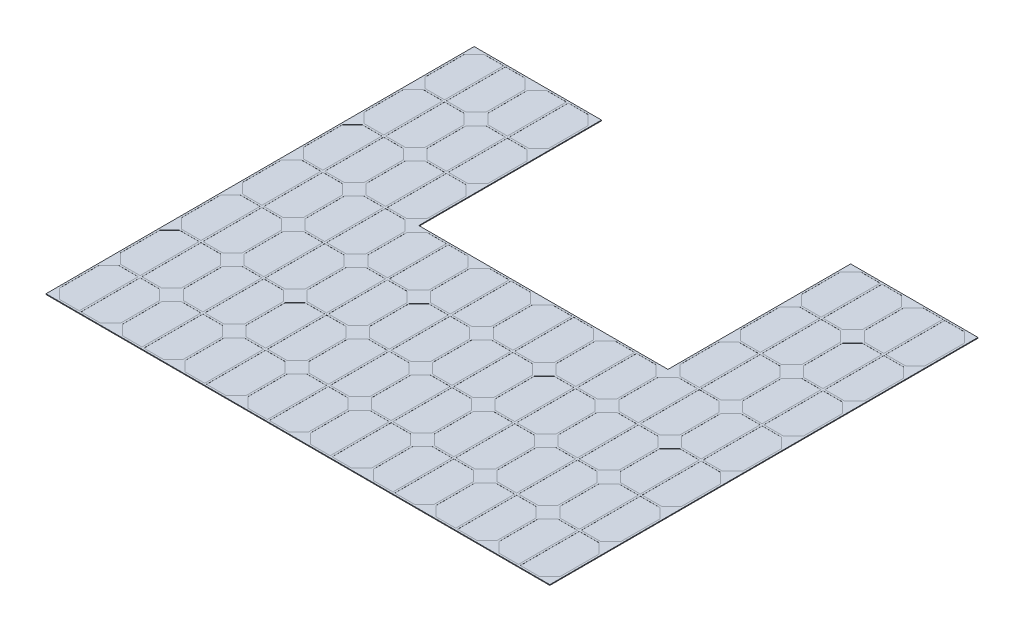
SolidWorks part; units mm, degrees
ref_plane "Front Plane" through (0, 0, 0) normal (0, 0, 1) x (1, 0, 0)
ref_plane "Top Plane" through (0, 0, 0) normal (0, 1, 0) x (1, 0, 0)
ref_plane "Right Plane" through (0, 0, 0) normal (1, 0, 0) x (0, 0, -1)
sketch "Sketch1" plane through (0, 0, 0) normal (0, 1, 0) x (1, 0, 0)
  line L0 (-102.0578, 273.2823) -> (-102.0578, 25.7823)
  line L1 (-274.5578, 273.2823) -> (-102.0578, 273.2823)
  line L2 (-274.5578, 273.2823) -> (-274.5578, -306.7177)
  line L3 (-274.5578, -306.7177) -> (407.9422, -306.7177)
  line L4 (407.9422, 273.2823) -> (407.9422, -306.7177)
  line L5 (-102.0578, 25.7823) -> (235.4422, 25.7823)
  line L6 (235.4422, 25.7823) -> (235.4422, 273.2823)
  line L7 (235.4422, 273.2823) -> (407.9422, 273.2823)
  dimension "D1" = 580
  dimension "D2" = 682.5
  dimension "D3" = 172.5
  dimension "D4" = 172.5
  dimension "D5" = 247.5
extrude "Boss-Extrude1" add sketch "Sketch1" along normal blind 1 contours L2 L3 L4 L7 L6 L5 L0 L1
sketch "Sketch2" plane through (0, 1, 0) normal (0, 1, 0) x (1, 0, 0)
  line L0 (-272.0578, -237.7177) -> (-272.0578, -290.7177)
  line L1 (-272.0578, -290.7177) -> (-258.5578, -304.2177)
  line L2 (-258.5578, -304.2177) -> (-232.0578, -304.2177)
  line L3 (-232.0578, -304.2177) -> (-232.0578, -224.2177)
  line L4 (-232.0578, -224.2177) -> (-258.5578, -224.2177)
  line L5 (-258.5578, -224.2177) -> (-272.0578, -237.7177)
  line L6 (-274.5578, 273.2823) -> (-274.5578, -306.7177) construction
  line L7 (-274.5578, -306.7177) -> (407.9422, -306.7177) construction
  line L8 (-230.8078, -139.2177) -> (-230.8078, -217.2899) construction
  line L9 (-203.0578, -224.2177) -> (-189.5578, -237.7177)
  line L10 (-229.5578, -224.2177) -> (-203.0578, -224.2177)
  line L11 (-229.5578, -304.2177) -> (-229.5578, -224.2177)
  line L12 (-203.0578, -304.2177) -> (-229.5578, -304.2177)
  line L13 (-189.5578, -290.7177) -> (-203.0578, -304.2177)
  line L14 (-189.5578, -237.7177) -> (-189.5578, -290.7177)
  dimension "D1" = 2.5
  dimension "D2" = 40
  dimension "D3" = 80
  dimension "D4" = 13.5
  dimension "D5" = 2.5
  dimension "D6" = 13.5
  dimension "D7" = 13.5
  dimension "D8" = 13.5
  dimension "D9" = 1.25
extrude "Cut-Extrude1" cut sketch "Sketch2" against normal blind 0.11
pattern_linear "LPattern1" count 8 spacing 85 along (1, 0, 0) count 7 spacing 82.5 along (0, 0, -1) of "Cut-Extrude1"
